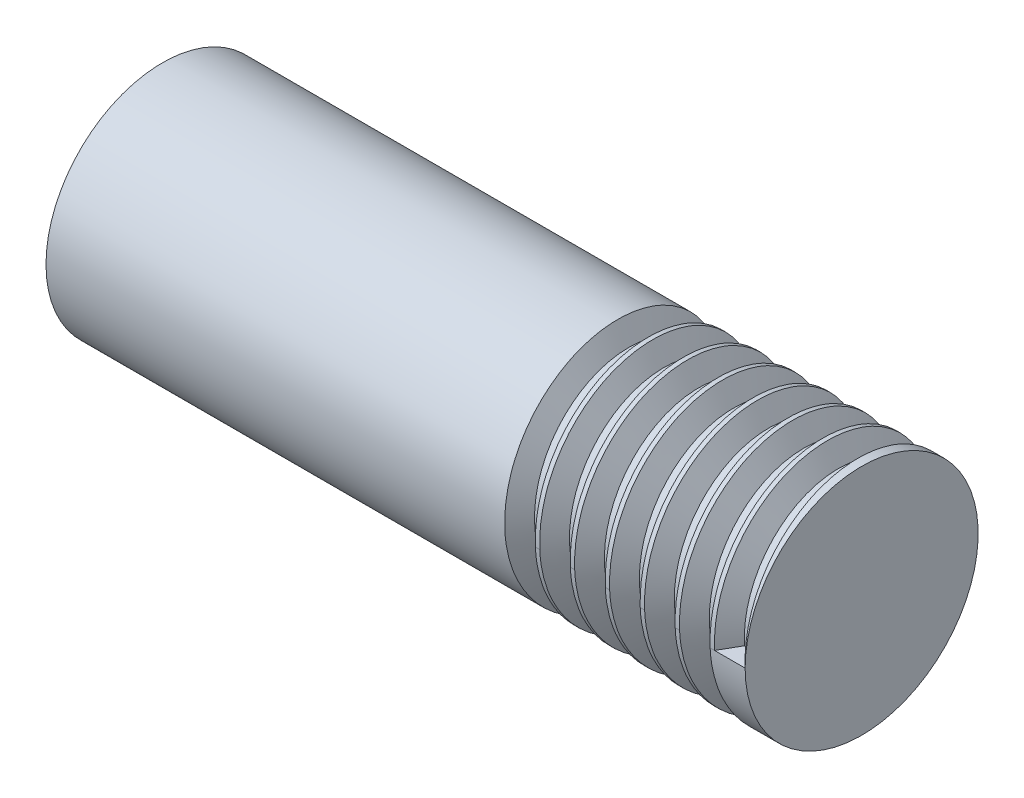
SolidWorks part; units mm, degrees
ref_plane "Front Plane" through (0, 0, 0) normal (0, 0, 1) x (1, 0, 0)
ref_plane "Top Plane" through (0, 0, 0) normal (0, 1, 0) x (1, 0, 0)
ref_plane "Right Plane" through (0, 0, 0) normal (1, 0, 0) x (0, 0, -1)
sketch "Sketch1" plane through (0, 0, 0) normal (1, 0, 0) x (0, 0, -1)
  circle A0 centre (0, 0) radius 5
extrude "Boss-Extrude1" add sketch "Sketch1" along normal blind 30
thread "Thread1" pitch 1.5 method cut profile "Thread Profile1" start angle 0, offset 0, length 10, pitch 1.5, diameter 10
ref_plane "Plane1" through (30, 0, 5) normal (0, -1, 0) x (0, 0, 1)
sketch "Thread Profile1" plane through (30, 0, 5) normal (0, -1, 0) x (0, 0, 1)
  line L0 (0, 0) -> (0, 1.5) construction
  line L11 (0, 0) -> (0, 1.3125)
  line L12 (0, 1.3125) -> (-0.8119, 0.8437)
  line L13 (-0.8119, 0.8437) -> (-0.8119, 0.4687)
  line L15 (-0.8119, 0.4687) -> (0, 0)
  line L17 (-0.8119, 0.6562) -> (0, 0.6562) construction
  point P2 (0, 0)
  dimension "Pitch" = 1.5
  dimension "Profile_Angle" = 60
  dimension "Profile_Land" = 0.375
  dimension "Profile_Height" = 0.8119
